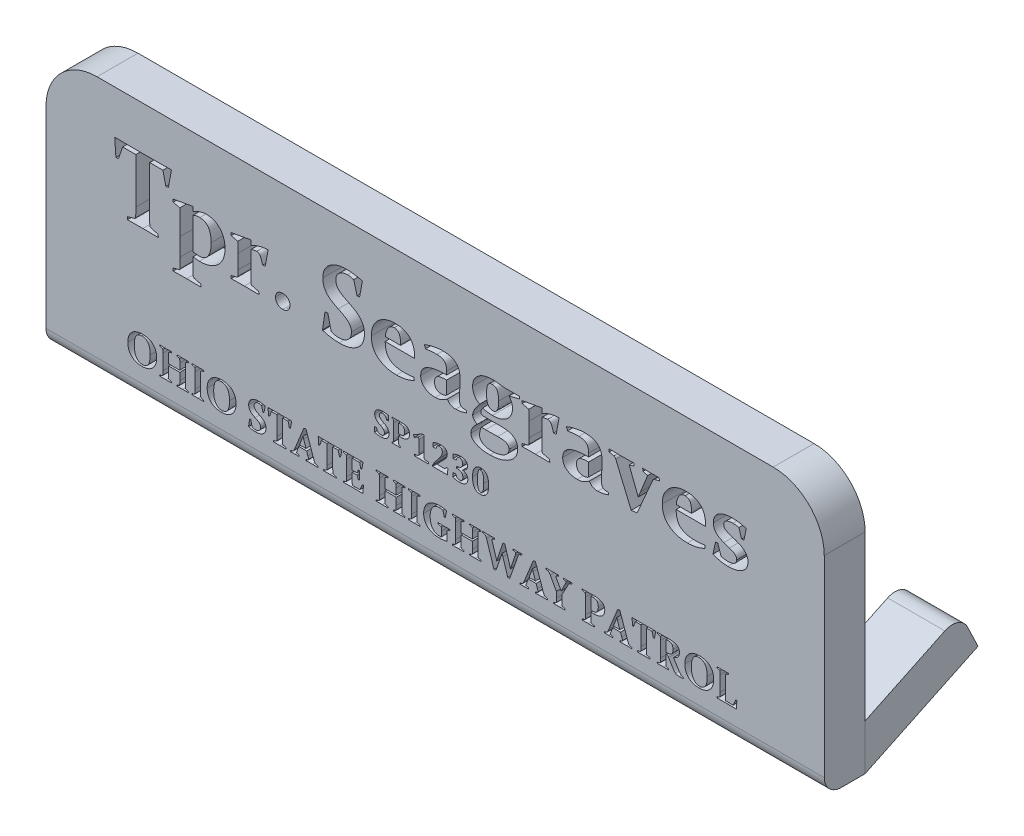
SolidWorks part; units mm, degrees
ref_plane "Front Plane" through (0, 0, 0) normal (0, 0, 1) x (1, 0, 0)
ref_plane "Top Plane" through (0, 0, 0) normal (0, 1, 0) x (1, 0, 0)
ref_plane "Right Plane" through (0, 0, 0) normal (1, 0, 0) x (0, 0, -1)
sketch "Sketch1" plane through (0, 0, 0) normal (0, 0, 1) x (1, 0, 0)
  line L1 (-108.803, -40.1851) -> (119.797, -40.1851)
  line L2 (-108.803, -40.1851) -> (-108.803, 21.3149)
  line L3 (-93.803, 36.3149) -> (104.797, 36.3149)
  line L4 (119.797, -40.1851) -> (119.797, 21.3149)
  arc A0 (104.797, 36.3149) -> (119.797, 21.3149) centre (104.797, 21.3149) cw
  arc A1 (-108.803, 21.3149) -> (-93.803, 36.3149) centre (-93.803, 21.3149) cw
  point P6 (119.797, 36.3149)
  dimension "D3" = 15
  dimension "D1" = 228.6
  dimension "D2" = 76.5
extrude "Boss-Extrude1" add sketch "Sketch1" along normal blind 12
sketch "Sketch2" plane through (119.797, 0, 0) normal (1, 0, 0) x (0, 0, -1)
  line L0 (0, -40.1851) -> (33.1567, -24.3437)
  line L1 (33.1567, -24.3437) -> (27.9311, -13.4062)
  line L2 (27.9311, -13.4062) -> (0, -26.7509)
  line L3 (0, -40.1851) -> (0, 21.3149) construction
  line L4 (0, -26.7509) -> (0, -40.1851)
extrude "Boss-Extrude2" add sketch "Sketch2" along normal blind 0.001 and the other way blind 228.6
sketch "Sketch3" plane through (0, -32.7169, -15.6312) normal (0, -0.9023, -0.4311) x (1, 0, 0)
  line L0 (-108.803, 17.3237) -> (119.797, 17.3237) construction
  line L1 (-92.003, 17.3237) -> (102.997, 17.3237)
  line L2 (-92.003, 17.3237) -> (-92.003, -19.423)
  line L3 (-92.003, -19.423) -> (102.997, -19.423)
  line L4 (102.997, 17.3237) -> (102.997, -19.423)
  line L5 (-108.803, -19.423) -> (119.798, -19.423) construction
  line L6 (-108.803, 17.3237) -> (-108.803, -19.423) construction
  line L7 (119.797, 17.3237) -> (119.798, -19.423) construction
  dimension "D1" = 195
  dimension "D2" = 16.8
  dimension "D3" = 16.8
extrude "Cut-Extrude1" cut sketch "Sketch3" against normal blind 13
fillet "Fillet2" radius 5 1 edges at (5.497, -40.1851, 12)
fillet "Fillet3" radius 5 1 edges at (5.497, -28.4551, 5.6043)
sketch "Sketch4" plane through (0, 0, 12) normal (0, 0, 1) x (1, 0, 0)
  text T0 "Tpr. Seagraves" font "Constantia" height in points 72
extrude "Cut-Extrude2" cut sketch "Sketch4" against normal blind 7
sketch "Sketch5" plane through (0, 0, 12) normal (0, 0, 1) x (1, 0, 0)
  text T0 "OHIO STATE HIGHWAY PATROL " font "Constantia" height in points 30
extrude "Cut-Extrude3" cut sketch "Sketch5" against normal blind 7
fillet "Fillet4" radius 5 2 edges at (-100.403, -13.4062, -27.9311) (111.3975, -13.4062, -27.9311)
sketch "Sketch6" plane through (0, 0, 12) normal (0, 0, 1) x (1, 0, 0)
  text T0 "SP1230" font "Cambria" height in points 24
extrude "Cut-Extrude4" cut sketch "Sketch6" against normal blind 7
sketch "Sketch8" plane through (0, -32.7169, -15.6312) normal (0, -0.9023, -0.4311) x (1, 0, 0)
  text T0 "NS" font "Dutch801 Rm BT" height in points 26
extrude "Cut-Extrude5" cut sketch "Sketch8" against normal blind 5
